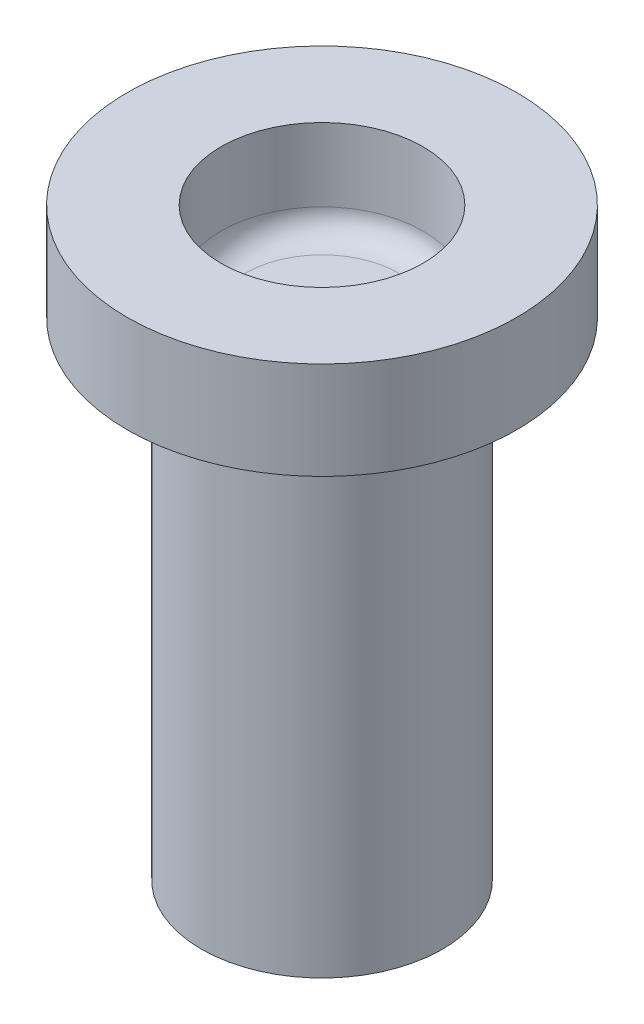
SolidWorks part; units mm, degrees
material "PET"
ref_plane "Front Plane" through (0, 0, 0) normal (0, 0, 1) x (1, 0, 0)
ref_plane "Top Plane" through (0, 0, 0) normal (0, 1, 0) x (1, 0, 0)
ref_plane "Right Plane" through (0, 0, 0) normal (1, 0, 0) x (0, 0, -1)
sketch "Sketch1" plane through (0, 0, 0) normal (0, 1, 0) x (1, 0, 0)
  circle A1 centre (0, 0) radius 2.475
  circle A2 centre (0, 0) radius 1.5
  dimension "D1" = 4.95
  dimension "D2" = 3
extrude "Boss-Extrude1" add sketch "Sketch1" along normal blind 5
extrude "Boss-Extrude2" add sketch "Sketch1<2>" along normal blind 5 from surface contours A1 A2 | A2 region at (-2.405, 0, 0) region at (0, 0, 0) starting at face at (0, 5, 2.475)
sketch "Sketch1<2>" plane through (0, 0, 0) normal (0, 1, 0) x (1, 0, 0) same geometry as "Sketch1"
sketch "Sketch2" plane through (0, 10, 0) normal (0, 1, 0) x (1, 0, 0)
  circle A1 centre (0, 0) radius 4
  circle A2 centre (0, 0) radius 2.075
  circle M4 centre (0, 0) radius 2.475
  dimension "D1" = 4.15
  dimension "D2" = 8
extrude "Boss-Extrude3" add sketch "Sketch2" along normal blind 2 contours M4 | A1 M4 | M4 | M4 region at (-3.8869, 10, 0) region at (-2.405, 10, 0)
fillet "Fillet1" radius 0.5 2 edges at (0, 10, 2.075) (0, 10, 2.475)
